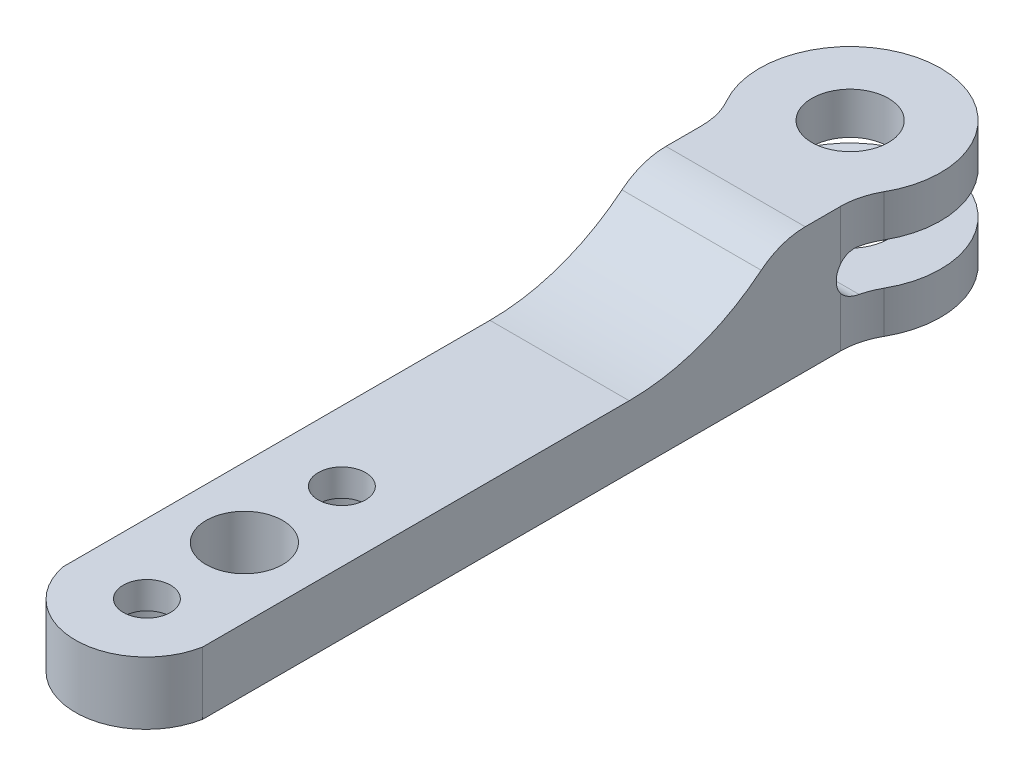
SolidWorks part; units mm, degrees
material "Nylon 101"
ref_plane "Front Plane" through (0, 0, 0) normal (0, 0, 1) x (1, 0, 0)
ref_plane "Top Plane" through (0, 0, 0) normal (0, 1, 0) x (1, 0, 0)
ref_plane "Right Plane" through (0, 0, 0) normal (1, 0, 0) x (0, 0, -1)
sketch "Sketch1" plane through (0, 0, 0) normal (0, 1, 0) x (1, 0, 0)
  line L2 (-5, -21.75) -> (-5, 21.75)
  line L4 (5, -21.75) -> (5, 21.75)
  line L5 (-5, -21.75) -> (5, 21.75) construction
  line L6 (-5, 21.75) -> (5, -21.75) construction
  arc A2 (-5, -21.75) -> (5, -21.75) centre (0, -21.75) ccw
  arc A3 (5, 21.75) -> (-5, 21.75) centre (0, 21.75) ccw
  point P0 (0, 0)
  dimension "D1" = 43.5
  dimension "D2" = 10
extrude "Boss-Extrude1" add sketch "Sketch1" along normal blind 4.5
ref_plane "Plane1" through (0, 4.5, 0) normal (0, 1, 0) x (1, 0, 0)
sketch "Sketch2" plane through (0, 4.5, 0) normal (0, 1, 0) x (1, 0, 0)
  circle A0 centre (0, 21.75) radius 2.75
  circle A1 centre (0, -21.75) radius 2.75
  arc A4 (5, 21.75) -> (-5, 21.75) centre (0, 21.75) ccw construction
  arc A5 (-5, -21.75) -> (5, -21.75) centre (0, -21.75) ccw construction
  dimension "D1" = 5.5
extrude "Cut-Extrude1" cut sketch "Sketch2" against normal through all
ref_plane "Plane2" through (0, 4.5, 0) normal (0, 1, 0) x (1, 0, 0)
sketch "Sketch3" plane through (0, 0, 0) normal (0, 1, 0) x (1, 0, 0)
  line L0 (-5, 21.75) -> (-5, -21.75) construction
  line L2 (-5, 17.5967) -> (-5, 11.5967)
  line L3 (-5, 11.5967) -> (5, 11.5967)
  line L4 (5, 17.5967) -> (5, 11.5967)
  line L5 (5, -21.75) -> (5, 21.75) construction
  arc A0 (5, 17.5967) -> (-5, 17.5967) centre (0, 21.75) ccw
  dimension "D1" = 13
  dimension "D2" = 6
extrude "Boss-Extrude2" add sketch "Sketch3" along normal blind 9
ref_plane "Plane3" through (0, 0, 0) normal (0, -1, 0) x (-1, 0, 0)
sketch "Sketch4" plane through (0, 0, 0) normal (0, -1, 0) x (-1, 0, 0)
  circle A0 centre (0, 21.75) radius 2.75
  arc A1 (5, 17.5967) -> (-5, 17.5967) centre (0, 21.75) ccw construction
  dimension "D1" = 5.5
extrude "Cut-Extrude2" cut sketch "Sketch4" against normal through all
ref_plane "Plane4" through (0, 0, 0) normal (0, -1, 0) x (-1, 0, 0)
sketch "Sketch6" plane through (0, 0, 0) normal (0, -1, 0) x (-1, 0, 0)
  line L0 (-5, -21.75) -> (-5, -29.75)
  line L1 (5, -21.75) -> (5, -29.75)
  arc A0 (-5, -21.75) -> (5, -21.75) centre (0, -21.75) ccw
  arc A1 (-5, -29.75) -> (5, -29.75) centre (0, -28.7973) ccw
  dimension "D1" = 8
extrude "Boss-Extrude3" add sketch "Sketch6" against normal up to surface (4.5 mm away) up to face at (0, 4.5, 24.5)
ref_plane "Plane5" through (0, 0, 0) normal (0, -1, 0) x (-1, 0, 0)
sketch "Sketch7" plane through (0, 0, 0) normal (0, -1, 0) x (-1, 0, 0)
  line L0 (0, -17.5) -> (0, 49982.5) construction
  line L1 (0, -21.75) -> (10.4981, -21.75) construction
  point P7 (0, -28.75)
  point P10 (0, -14.75)
  dimension "D2" = 7
hole_wizard "CBORE for M3 SBHCS1" positions "Sketch10" profile "Sketch11" counterbore size "M3" standard "ANSI Metric" end condition up to next
sketch "Sketch10" plane through (0, 0, 0) normal (0, -1, 0) x (-1, 0, 0)
  point P0 (0, -14.75)
  point P6 (0, -28.75)
sketch "Sketch11" plane through (0, 0, 14.75) normal (1, 0, 0) x (0, 0, -1)
  line L0 (0, 0) -> (0, 4.5)
  line L1 (0, 4.5) -> (1.7, 4.5)
  line L3 (1.7, 4.5) -> (1.7, 2.55)
  line L4 (1.7, 2.55) -> (3.125, 2.55)
  line L5 (3.125, 2.55) -> (3.125, 0)
  line L7 (3.125, 0) -> (0, 0)
  line L11 (0, -6.35) -> (0, 107.95) construction
  dimension "Thru Hole Dia." = 3.4
  dimension "Thru Hole Depth" = 4.5
  dimension "C'Bore Dia." = 6.25
  dimension "C'Bore Depth" = 2.55
fillet "Fillet1" radius 15 1 edges at (0, 4.5, -11.5967)
ref_plane "Plane7" through (-6.5, 0, 0) normal (-1, 0, 0) x (0, 0, 1)
sketch "Sketch12" plane through (-6.5, 0, 0) normal (-1, 0, 0) x (0, 0, 1)
  line L0 (-28.25, 9) -> (-28.25, 0)
  line L2 (-28.25, 6) -> (-17.25, 6)
  line L3 (-28.25, 6) -> (-28.25, 3)
  line L4 (-28.25, 3) -> (-17.25, 3)
  arc A0 (-17.25, 3) -> (-17.25, 6) centre (-17.25, 4.5) ccw
  point P9 (-28.25, 4.5)
  dimension "D1" = 3
  dimension "D2" = 11
extrude "Cut-Extrude3" cut sketch "Sketch12" against normal up to next contours A0 L2 L3 L4
fillet "Fillet2" radius 5 5 edges at (0, 9, -11.5967) (5, 1.5, -17.5967) (5, 7.5, -17.5967) (-5, 1.5, -17.5967) (-5, 7.5, -17.5967)
sketch "Sketch13" plane through (0, 9, 0) normal (0, 1, 0) x (1, 0, 0)
  circle A0 centre (0, 21.75) radius 2.75
  circle A1 centre (0, 21.75) radius 4.75
  circle A2 centre (0, 21.75) radius 2.75 construction
  dimension "D1" = 2
